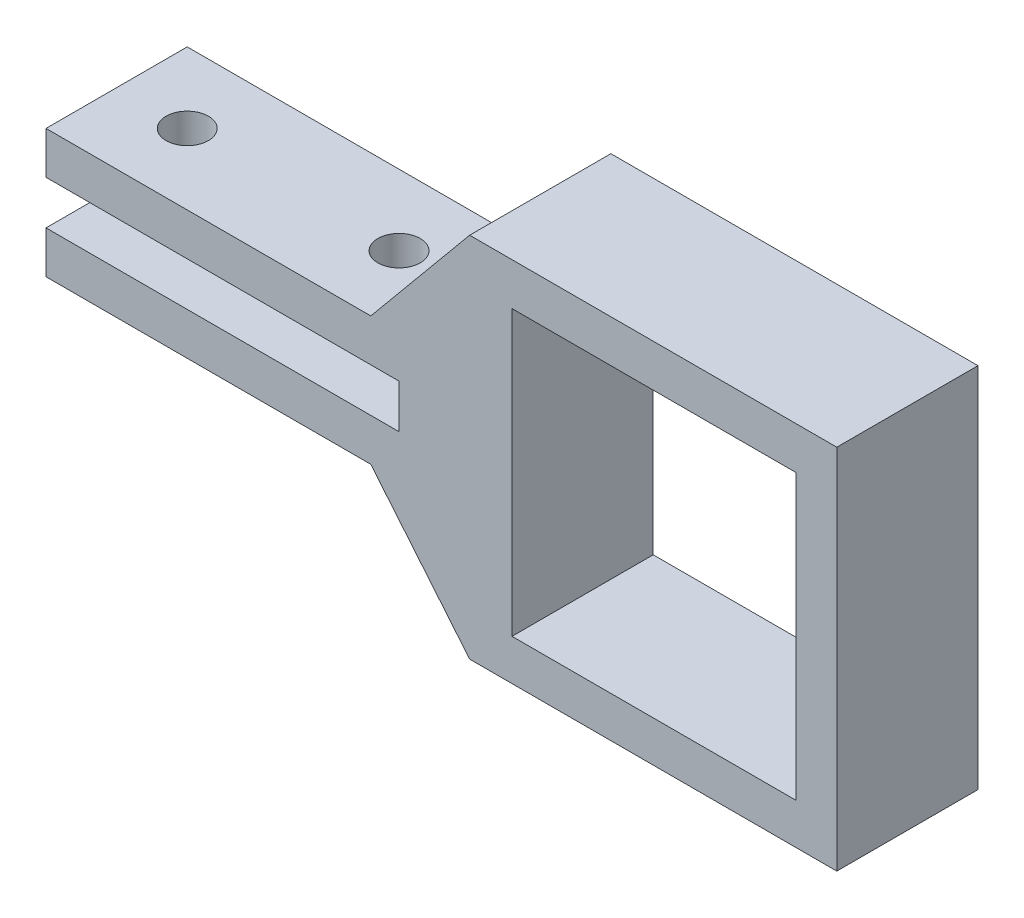
SolidWorks part; units mm, degrees
ref_plane "前视基准面" through (0, 0, 0) normal (0, 0, 1) x (1, 0, 0)
ref_plane "上视基准面" through (0, 0, 0) normal (0, 1, 0) x (1, 0, 0)
ref_plane "右视基准面" through (0, 0, 0) normal (1, 0, 0) x (0, 0, -1)
sketch "草图1" plane through (0, 0, 0) normal (0, 0, 1) x (1, 0, 0)
  line L68 (-21.1315, 0) -> (10.2214, 0) construction
  line L78 (-30, 4.55) -> (-30, 1.55)
  line L79 (-30, 4.55) -> (-7, 4.55)
  line L82 (-30, 1.55) -> (-5, 1.55)
  line L83 (0, 4.55) -> (0, 13) construction
  line L84 (0, 13) -> (26, 13)
  line L85 (0, -13) -> (26, -13)
  line L86 (0, -4.55) -> (0, -13) construction
  line L87 (-30, -1.55) -> (-5, -1.55)
  line L90 (-30, -4.55) -> (-7, -4.55)
  line L91 (-30, -4.55) -> (-30, -1.55)
  line L92 (-5, 1.55) -> (-5, -1.55)
  line L93 (26, 13) -> (26, -13)
  line L94 (0, 1.55) -> (0, 4.55) construction
  line L95 (0, -1.55) -> (0, -4.55) construction
  line L96 (0, -13) -> (-7, -4.55)
  line L97 (0, 13) -> (-7, 4.55)
  line L98 (-7, 4.55) -> (0, 4.55) construction
  line L99 (-7, -4.55) -> (0, -4.55) construction
  dimension "D1" = 30
  dimension "D2" = 26
  dimension "D3" = 3.1
  dimension "D4" = 25
  dimension "D5" = 7
  dimension "D6" = 7
  dimension "D8" = 26
  dimension "5" = 3
extrude "凸台-拉伸1" add sketch "草图1" along normal blind 10 contours L85 L93 L84 L97 L79 L78 L82 L92 L87 L91 L90 L96
sketch "草图5" plane through (0, 0, 10) normal (0, 0, 1) x (1, 0, 0)
  line L0 (3, 10) -> (3, -10.1)
  line L1 (3, -10.1) -> (23.1, -10.1)
  line L3 (23.1, 10) -> (3, 10)
  line L17 (23.1, 10) -> (23.1, -10.1)
  dimension "D1" = 20.1
  dimension "D2" = 20.1
extrude "切除-拉伸1" cut sketch "草图5" against normal blind 30
sketch "草图7" plane through (0, 4.55, 0) normal (0, 1, 0) x (1, 0, 0)
  line L0 (-25, -5) -> (-30, -5) construction
  line L2 (-30, -10) -> (-30, 0) construction
  line L3 (-25, -5) -> (-25, 0) construction
  line L4 (-30, 0) -> (-7, 0) construction
  circle A0 centre (-25, -5) radius 1.5
  circle A1 centre (-10, -5) radius 1.5
  dimension "D1" = 3
  dimension "D2" = 5
  dimension "D3" = 5
  dimension "D4" = 2
extrude "切除-拉伸5" cut sketch "草图7" against normal up to surface (9.1 mm away) up to face at (-18.5, -4.55, 5)
